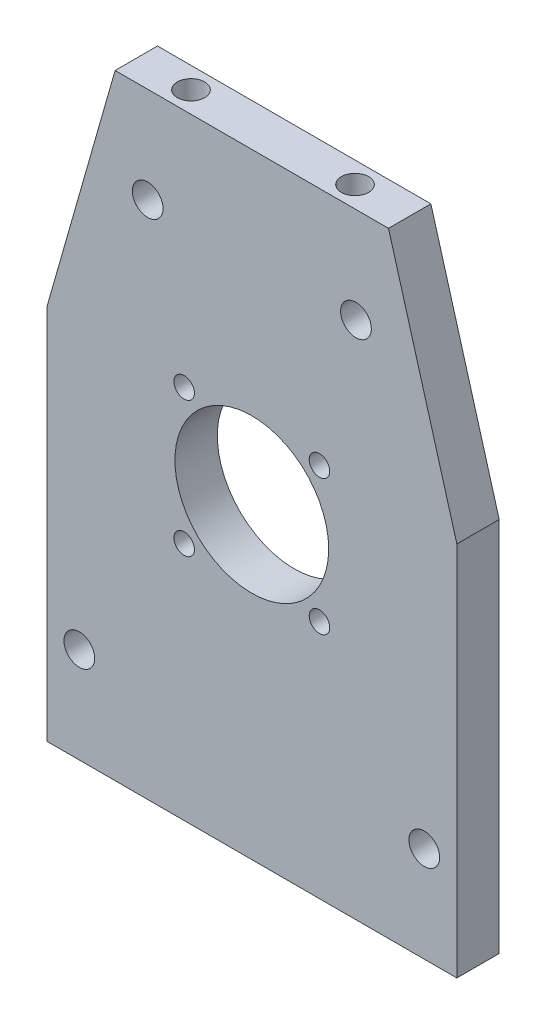
SolidWorks part; units mm, degrees
material "6061 Alloy"
ref_plane "Front Plane" through (0, 0, 0) normal (0, 0, 1) x (1, 0, 0)
ref_plane "Top Plane" through (0, 0, 0) normal (0, 1, 0) x (1, 0, 0)
ref_plane "Right Plane" through (0, 0, 0) normal (1, 0, 0) x (0, 0, -1)
sketch "Sketch1" plane through (0, 0, 0) normal (0, 0, 1) x (1, 0, 0)
  line L0 (-20, 45) -> (20, 45)
  line L5 (-30, -45) -> (30, -45)
  line L6 (0, 45) -> (0, -45) construction
  line L7 (-20, 45) -> (-30, 10)
  line L8 (-30, 10) -> (-30, -45)
  line L9 (30, 10) -> (30, -45)
  line L10 (20, 45) -> (30, 10)
  dimension "D1" = 90
  dimension "D2" = 60
  dimension "D3" = 40
  dimension "D4" = 55
extrude "1/4" add sketch "Sketch1" along normal mid plane 6.2
sketch "Sketch3" plane through (0, 0, 0) normal (0, 0, 1) x (1, 0, 0)
  circle A0 centre (0, 0) radius 11.25
  dimension "D1" = 22.5
extrude "Cut-Extrude2" cut sketch "Sketch3" along normal up to surface (3.1 mm away) and the other way blind 8 up to face at (0, 3.3333, 3.1)
sketch "Sketch2" plane through (0, 0, 3.1) normal (0, 0, 1) x (1, 0, 0)
  line L0 (-9.8995, 9.8995) -> (0, 0) construction
  line L1 (20, 45) -> (-20, 45) construction
  circle A0 centre (0, 0) radius 14 construction
  circle A1 centre (-9.8995, 9.8995) radius 1.5
  circle A2 centre (9.8995, 9.8995) radius 1.5
  circle A3 centre (9.8995, -9.8995) radius 1.5
  circle A4 centre (-9.8995, -9.8995) radius 1.5
  point P16 (0, 0)
  dimension "D1" = 28
  dimension "D3" = 3
  dimension "D2" = 45
  dimension "D4" = 4
extrude "M3_DRILL" cut sketch "Sketch2" against normal up to surface (6.2 mm away) up to face at (11.25, 0, -3.1)
sketch "Sketch4" plane through (0, 45, 0) normal (0, 1, 0) x (1, 0, 0)
  line L0 (0, -3.1) -> (0, 3.1) construction
  line L1 (0, 0) -> (-12, 0) construction
  line L2 (20, -3.1) -> (-20, -3.1) construction
  line L3 (20, 3.1) -> (-20, 3.1) construction
  circle A0 centre (-12, 0) radius 2
  circle A1 centre (12, 0) radius 2
  dimension "D2" = 4
  dimension "D1" = 12
extrude "M4_DRILL" cut sketch "Sketch4" against normal blind 8
sketch "Sketch5" plane through (0, -45, 0) normal (0, -1, 0) x (-1, 0, 0)
  line L0 (0, -3.1) -> (0, 3.1) construction
  line L2 (0, 0) -> (-20, 0) construction
  line L3 (30, -3.1) -> (-30, -3.1) construction
  line L4 (30, 3.1) -> (-30, 3.1) construction
  circle A0 centre (-20, 0) radius 2
  circle A1 centre (20, 0) radius 2
  circle A2 centre (0, 0) radius 2
  dimension "D1" = 4
  dimension "D2" = 20
extrude "M4_DRILL2" cut sketch "Sketch5" against normal blind 8
sketch "Sketch6" plane through (0, 0, 3.1) normal (0, 0, 1) x (1, 0, 0)
  line L2 (0, 0) -> (0, -45.222) construction
  line L4 (20, 45) -> (-20, 45) construction
  line L5 (-30, -45) -> (30, -45) construction
  line L6 (-30, 10) -> (-30, -45) construction
  circle A0 centre (-25.2375, -31) radius 2.25
  circle A1 centre (25.2375, -31) radius 2.25
  circle A2 centre (-15.2375, 31) radius 2.25
  circle A3 centre (15.2375, 31) radius 2.25
  dimension "D1" = 4.5
  dimension "D6" = 4.5
  dimension "D2" = 14
  dimension "D3" = 4.7625
  dimension "D4" = 14
  dimension "D5" = 4.7625
extrude "M4_through" cut sketch "Sketch6" against normal up to surface (6.2 mm away) up to face at (-8.3995, -9.8995, -3.1)
